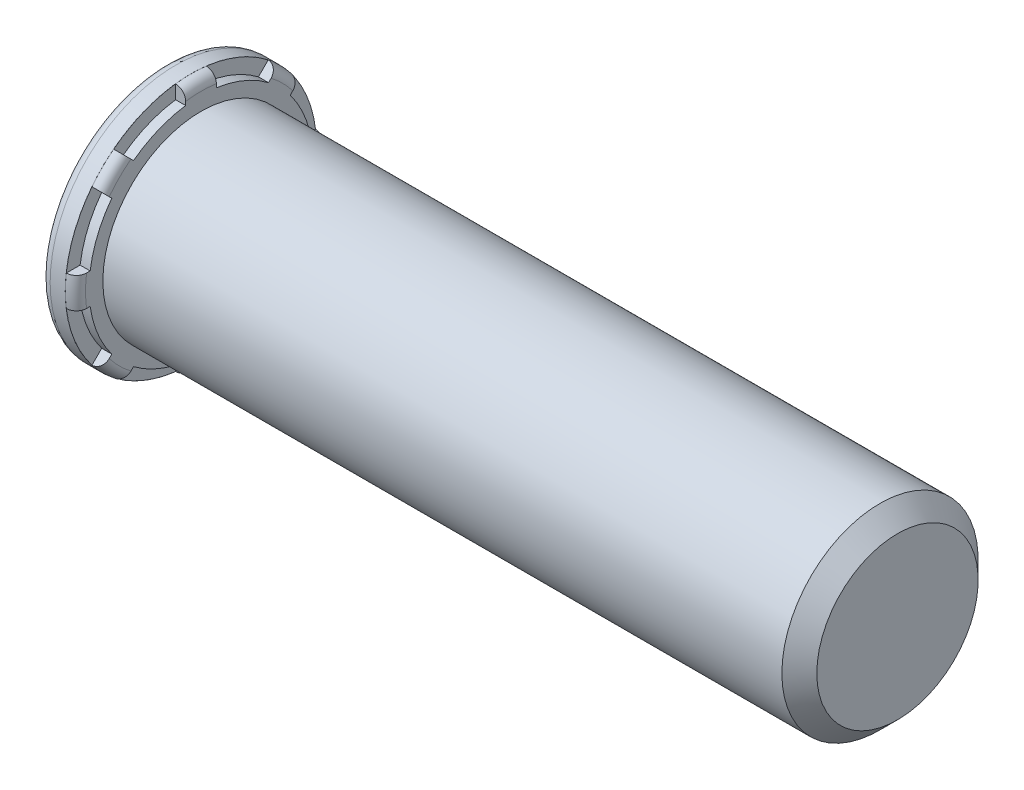
SolidWorks part; units mm, degrees
revolve "BaseBody" add sketch "BodySke" angle 360 about L6 other way angle 7.5
sketch "BodySke" plane through (0, 0, 0) normal (0, 0, 1) x (1, 0, 0)
  line L0 (-0.64, 2.944) -> (-0.64, 0)
  line L1 (0.2585, 2.9415) -> (0.2585, 2.5)
  line L3 (0.2585, 2.5) -> (17.555, 2.5)
  line L4 (18, 2.055) -> (18, 0)
  line L5 (18, 0) -> (-0.64, 0)
  line L6 (0, 0) -> (50.554, 0) construction
  line L8 (18, 2.055) -> (17.555, 2.5)
  line L9 (-0.384, 3.2) -> (0, 3.2)
  line L10 (0.0025, 3.1975) -> (0, 3.1975)
  line L11 (0.8, 19.05) -> (0.8, -3.175) construction
  line L12 (0, 3.1975) -> (0, 3.2)
  arc A0 (-0.64, 2.944) -> (-0.384, 3.2) centre (-0.384, 2.944) cw
  arc A1 (0.0025, 3.1975) -> (0.2585, 2.9415) centre (0.0025, 2.9415) cw
  dimension "Fillet_rad" = 0.256
  dimension "Minor_dia" = 4.11
  dimension "Diameter" = 5
  dimension "T_dim" = 0.64
  dimension "H_dia" = 6.4
  dimension "D2" = 0.0025
  dimension "D3" = 0.0025
  dimension "Length" = 18
  dimension "Advance" = 0.8
cosmetic thread "ThreadCosmetic" [suppressed] parameters "Thread_length"=15.7, "Thread_minor"=4.11
ref_plane "Plane1" through (0, 0, 0) normal (0, 0, 1) x (1, 0, 0)
ref_plane "Plane2" through (0, 0, 0) normal (0, 1, 0) x (1, 0, 0)
ref_plane "Plane3" through (0, 0, 0) normal (1, 0, 0) x (0, 0, -1)
sketch "ThdSchSke" plane through (0, 0, 0) normal (0, 0, 1) x (1, 0, 0)
  line L0 (2.3, -2.055) -> (1.9884, -2.5)
  line L1 (2.3, -2.055) -> (2.6116, -2.5)
  line L2 (2.6116, -2.5) -> (2.6116, -3.125)
  line L3 (-3.175, 0) -> (5.1513, 0) construction
  line L4 (0, -3.2) -> (0, 3.2) construction
  line L5 (2.6116, -3.125) -> (1.9884, -3.125)
  line L6 (1.9884, -3.125) -> (1.9884, -2.5)
  dimension "Diameter" = 5
  dimension "Thread_minor" = 4.11
  dimension "Start" = 2.3
revolve "ThreadSchematic" [suppressed] cut sketch "ThdSchSke" angle 360 about L3
pattern_linear "ThdSchPat" [suppressed]
sketch "RibCutSke" plane through (0.2585, 1.7944, -0.091) normal (1, 0, 0) x (0, 0, -1)
  line L0 (0.3001, 1.0286) -> (0.3001, 1.3816)
  line L1 (1.6287, 0.4783) -> (1.8783, 0.7279)
  line L2 (0.3001, 0.6748) -> (0.3001, 2.4006) construction
  line L3 (-0.091, -1.7944) -> (-0.091, 5.0239) construction
  line L4 (-0.091, -1.7944) -> (0.3001, 0.6748) construction
  line L5 (-0.091, -1.7944) -> (1.3785, 0.2281) construction
  line L6 (1.3785, 0.2281) -> (2.6039, 1.4535) construction
  circle A0 centre (-0.091, -1.7944) radius 2.9415 construction
  arc A1 (1.6287, 0.4783) -> (0.3001, 1.0286) centre (-0.091, -1.7944) ccw
  arc A2 (1.8783, 0.7279) -> (0.3001, 1.3816) centre (-0.091, -1.7944) ccw
  circle A4 centre (-0.091, -1.7944) radius 2.5 construction
  dimension "Rib_root_half_angle" = 9
  dimension "Rib_root_gap_angle" = 27
  dimension "Angle" = 45
extrude "RibCut" cut sketch "RibCutSke" against normal blind 0.2561
pattern_circular "RibCutsPat" count 8 every 45 about axis through (0, 0, 0) along (1, 0, 0) of "RibCut"
equation "' \"Length@BodySke\" = 18"
equation "' \"H_dia@BodySke\" = 6.4"
equation "' \"Start@ThdSchSke\" = 2.3"
equation "' \"T_dim@BodySke\" = 0.64"
equation "' \"Diameter@BodySke\" = 5"
equation "' \"Minor_dia@BodySke\" = 4.11"
equation "' \"Advance@BodySke\" = 0.8"
equation "\"Fillet_rad@BodySke\" =  \"T_dim@BodySke\" * 0.4"
equation "\"Num_ribs@RibCutsPat\" = 8"
equation "\"Angle@RibCutSke\" =\"Angle@RibCutsPat\""
equation "\"Rib_root_half_angle@RibCutSke\" = \"Angle@RibCutSke\" / 5"
equation "\"Rib_root_gap_angle@RibCutSke\" = \"Angle@RibCutSke\" - (2 * \"Rib_root_half_angle@RibCutSke\" )"
equation "\"Rib_root_dia@RibCutSke\" = \"Diameter@BodySke\""
equation "\"Inner_dia@RibCutSke\" = ( \"H_dia@BodySke\" + \"Diameter@BodySke\" ) / 2"
equation "\"Outer_dia@RibCutSke\" = \"H_dia@BodySke\""
equation "\"Depth@RibCut\" =  \"Fillet_rad@BodySke\" + 0.0001"
equation "\"Thread_length@ThreadCosmetic\" = \"Length@BodySke\" - \"Start@ThdSchSke\""
equation "\"Thread_minor@ThreadCosmetic\" = \"Minor_dia@BodySke\""
equation "\"Thread_minor@ThdSchSke\" = \"Minor_dia@BodySke\""
equation "\"Diameter@ThdSchSke\" = \"Diameter@BodySke\""
equation "\"Overcut@ThdSchSke\" = \"Diameter@BodySke\" * 1.25"
equation "\"Num_threads@ThdSchPat\" = int( \"Thread_length@ThreadCosmetic\" / \"Advance@BodySke\" + 0.999 )  + 1"
equation "\"Advance@ThdSchPat\" = \"Thread_length@ThreadCosmetic\" /  (\"Num_threads@ThdSchPat\" - 1) 'relax it"
equation "\"Num_threads@ThdSchPat\" = \"Num_threads@ThdSchPat\" - sgn( \"Num_threads@ThdSchPat\" - 1) '---chamfered tips only---"
